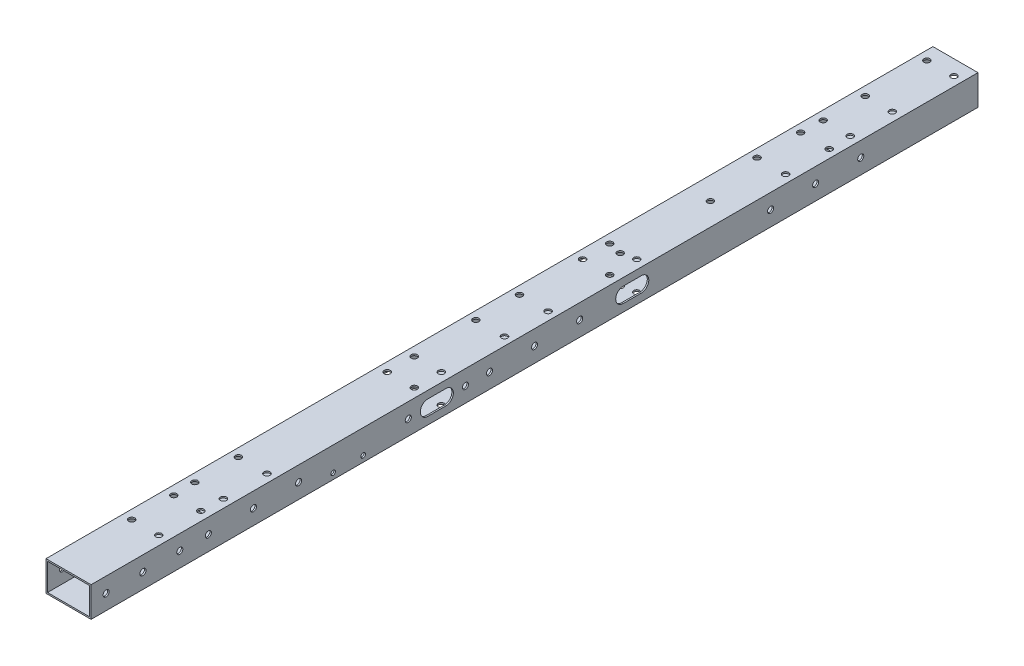
SolidWorks part; units mm, degrees
material "6063-T5"
ref_plane "前视基准面" through (0, 0, 0) normal (0, 0, 1) x (1, 0, 0)
ref_plane "上视基准面" through (0, 0, 0) normal (0, 1, 0) x (1, 0, 0)
ref_plane "右视基准面" through (0, 0, 0) normal (1, 0, 0) x (0, 0, -1)
sketch "草图1" plane through (0, 0, 0) normal (0, 0, 1) x (1, 0, 0)
  line L0 (-14, -9) -> (-14, 9)
  line L1 (-15, -10) -> (15, -10)
  line L2 (-15, -10) -> (-15, 10)
  line L3 (-15, 10) -> (15, 10)
  line L4 (15, -10) -> (15, 10)
  line L5 (0, 10) -> (0, -10) construction
  line L6 (-15, 0) -> (15, 0) construction
  line L7 (-14, 9) -> (14, 9)
  line L8 (14, -9) -> (14, 9)
  line L9 (-14, -9) -> (14, -9)
  point P0 (0, 0)
  dimension "D1" = 20
  dimension "D2" = 30
  dimension "D3" = 1
extrude "凸台-拉伸1" add sketch "草图1" along normal mid plane 590
sketch "草图2" [suppressed] plane through (15, 0, 0) normal (1, 0, 0) x (0, 0, -1)
  line L0 (-295, 10) -> (295, 10) construction
  line L1 (209, 10) -> (295, 10)
  line L2 (209, 10) -> (209, -10)
  line L3 (209, -10) -> (295, -10)
  line L4 (295, 10) -> (295, -10)
  dimension "D1" = 86
extrude "切除-拉伸1" [suppressed] cut sketch "草图2" against normal blind 60
sketch "草图4" [suppressed] plane through (0, 10, 0) normal (0, 1, 0) x (1, 0, 0)
  circle A0 centre (0, 0) radius 5
  dimension "D1" = 10
extrude "切除-拉伸3" [suppressed] cut sketch "草图4" against normal mid plane 64
sketch "草图5" plane through (0, 9, 0) normal (0, -1, 0) x (1, 0, 0)
  line L0 (-15, 295) -> (-15, -295) construction
  line L1 (-9.5, 14.5) -> (9.5, 14.5) construction
  line L2 (-9.5, 14.5) -> (-9.5, -14.5) construction
  line L3 (-9.5, -14.5) -> (9.5, -14.5) construction
  line L4 (9.5, 14.5) -> (9.5, -14.5) construction
  line L5 (-9.5, 14.5) -> (9.5, -14.5) construction
  line L6 (-9.5, -14.5) -> (9.5, 14.5) construction
  line L7 (-9.5, 201.5) -> (9.5, 201.5) construction
  line L8 (-9.5, 201.5) -> (-9.5, 172.5) construction
  line L13 (-9.5, 172.5) -> (9.5, 172.5) construction
  line L14 (9.5, 201.5) -> (9.5, 172.5) construction
  line L15 (-15, 295) -> (15, 295) construction
  line L16 (15, 295) -> (15, -295) construction
  line L17 (-9.5, -172.5) -> (9.5, -172.5) construction
  line L18 (-9.5, -172.5) -> (-9.5, -201.5) construction
  line L19 (-9.5, -201.5) -> (9.5, -201.5) construction
  line L20 (9.5, -172.5) -> (9.5, -201.5) construction
  line L21 (-15, -295) -> (15, -295) construction
  circle A4 centre (9.5, -201.5) radius 1.65 construction
  circle A5 centre (9.5, -172.5) radius 1.65 construction
  circle A6 centre (-9.5, -201.5) radius 1.65 construction
  circle A7 centre (-9.5, -172.5) radius 1.65 construction
  circle A8 centre (-9.5, -172.5) radius 2.025
  circle A9 centre (9.5, -172.5) radius 2.025
  circle A10 centre (-9.5, -201.5) radius 2.025
  circle A11 centre (9.5, -201.5) radius 2.025
  circle A20 centre (9.5, 172.5) radius 1.65 construction
  circle A21 centre (-9.5, 172.5) radius 1.65 construction
  circle A22 centre (9.5, 201.5) radius 1.65 construction
  circle A23 centre (-9.5, 201.5) radius 1.65 construction
  circle A24 centre (9.5, -14.5) radius 1.65 construction
  circle A25 centre (9.5, 14.5) radius 1.65 construction
  circle A26 centre (-9.5, -14.5) radius 1.65 construction
  circle A27 centre (-9.5, 14.5) radius 1.65 construction
  circle A28 centre (-9.5, -14.5) radius 2.025
  circle A29 centre (9.5, -14.5) radius 2.025
  circle A30 centre (-9.5, 14.5) radius 2.025
  circle A31 centre (9.5, 14.5) radius 2.025
  circle A32 centre (-9.5, 172.5) radius 2.025
  circle A33 centre (-9.5, 201.5) radius 2.025
  circle A34 centre (9.5, 201.5) radius 2.025
  circle A35 centre (9.5, 172.5) radius 2.025
  point P1 (0, 0)
  point P3 (-9.5, 187)
  dimension "D1" = 4.05
  dimension "D2" = 29
  dimension "D5" = 29
  dimension "D3" = 19
  dimension "D4" = 19
  dimension "D6" = 5.5
  dimension "D7" = 93.5
  dimension "D8" = 5.5
  dimension "D9" = 5.5
  dimension "D10" = 122.5
  dimension "D11" = 29
extrude "切除-拉伸4" cut sketch "草图5" against normal mid plane 10
sketch "草图7" plane through (0, -9, 0) normal (0, 1, 0) x (1, 0, 0)
  circle A0 centre (-9.5, 201.5) radius 3.8
  circle A1 centre (9.5, 201.5) radius 3.8
  circle A2 centre (-9.5, 172.5) radius 3.8
  circle A3 centre (9.5, 172.5) radius 3.8
  circle A4 centre (-9.5, 14.5) radius 3.8
  circle A5 centre (9.5, 14.5) radius 3.8
  circle A6 centre (-9.5, -14.5) radius 3.8
  circle A7 centre (9.5, -14.5) radius 3.8
  circle A8 centre (-9.5, -172.5) radius 3.8
  circle A9 centre (9.5, -172.5) radius 3.8
  circle A10 centre (-9.5, -201.5) radius 3.8
  circle A11 centre (9.5, -201.5) radius 3.8
  dimension "D1" = 7.6
extrude "切除-拉伸5" cut sketch "草图7" against normal mid plane 10
sketch "草图8" [suppressed] plane through (15, 0, 0) normal (1, 0, 0) x (0, 0, -1)
  circle A0 centre (-151, 0) radius 2.025 construction
  circle A1 centre (-185, 0) radius 2.025 construction
  circle A2 centre (-219, 0) radius 2.025 construction
  circle A3 centre (-151, 0) radius 2.025
  circle A4 centre (-185, 0) radius 2.025
  circle A5 centre (-219, 0) radius 2.025
  circle A6 centre (36, 0) radius 2.025 construction
  circle A7 centre (2, 0) radius 2.025 construction
  circle A8 centre (-32, 0) radius 2.025 construction
  circle A9 centre (36, 0) radius 2.025
  circle A10 centre (2, 0) radius 2.025
  circle A11 centre (-32, 0) radius 2.025
extrude "切除-拉伸6" [suppressed] cut sketch "草图8" against normal blind 74
sketch "草图9" [suppressed] plane through (-15, 0, 0) normal (-1, 0, 0) x (0, 0, 1)
  circle A0 centre (-155, 0) radius 2.025 construction
  circle A1 centre (-189, 5) radius 1.525 construction
  circle A2 centre (-203, 0) radius 2.025 construction
  circle A3 centre (-155, 0) radius 2.025
  circle A4 centre (-189, 5) radius 1.525
  circle A5 centre (-203, 0) radius 2.025
extrude "切除-拉伸7" [suppressed] cut sketch "草图9" against normal blind 114
sketch "草图10" [suppressed] plane through (0, -10, 0) normal (0, -1, 0) x (1, 0, 0)
  circle A0 centre (0, -75) radius 2.025 construction
  circle A1 centre (0, -109) radius 2.025 construction
  circle A2 centre (0, -143) radius 2.025 construction
  circle A3 centre (0, -75) radius 2.025
  circle A4 centre (0, -109) radius 2.025
  circle A5 centre (0, -143) radius 2.025
extrude "切除-拉伸8" [suppressed] cut sketch "草图10" against normal blind 70
sketch "草图11" plane through (15, 0, 0) normal (1, 0, 0) x (0, 0, -1)
  line L0 (-295, -10) -> (-295, 10) construction
  line L1 (-295, 10) -> (295, 10) construction
  circle A9 centre (-236, 0) radius 2.025 construction
  circle A10 centre (-260.5, 0) radius 2.025 construction
  circle A11 centre (-285, 0) radius 2.025 construction
  circle A12 centre (217, 0) radius 2.025
  circle A13 centre (187, 0) radius 2.025
  circle A14 centre (157, 0) radius 2.025
  circle A15 centre (30, 0) radius 2.025
  circle A16 centre (0, 0) radius 2.025
  circle A17 centre (-30, 0) radius 2.025
  circle A18 centre (-157, 0) radius 2.025
  circle A19 centre (-187, 0) radius 2.025
  circle A20 centre (-217, 0) radius 2.025
  circle A21 centre (-236, 0) radius 2.025
  circle A22 centre (-260.5, 0) radius 2.025
  circle A23 centre (-285, 0) radius 2.025
  dimension "D1" = 30
  dimension "D3" = 78
  dimension "D4" = 30
  dimension "D5" = 30
  dimension "D6" = 10
  dimension "D7" = 127
  dimension "D8" = 127
  dimension "D9" = 30
  dimension "D10" = 30
  dimension "D2" = 30
extrude "切除-拉伸9" cut sketch "草图11" against normal blind 113
sketch "草图12" [suppressed] plane through (0, 10, 0) normal (0, 1, 0) x (1, 0, 0)
  circle A0 centre (0, 36.5) radius 2.025 construction
  circle A1 centre (0, 18.5) radius 2.025 construction
  circle A2 centre (0, 36.5) radius 2.025
  circle A3 centre (0, 18.5) radius 2.025
extrude "切除-拉伸10" [suppressed] cut sketch "草图12" against normal blind 80
sketch "草图13" [suppressed] plane through (-15, 0, 0) normal (-1, 0, 0) x (0, 0, 1)
  circle A0 centre (28, 0) radius 2.025 construction
  circle A1 centre (3.5, 0) radius 2.025 construction
  circle A2 centre (28, 0) radius 2.025
  circle A3 centre (3.5, 0) radius 2.025
extrude "切除-拉伸11" [suppressed] cut sketch "草图13" against normal blind 80
sketch "草图14" [suppressed] plane through (0, -9, 0) normal (0, 1, 0) x (1, 0, 0)
  circle A0 centre (-7.5, 45.55) radius 1.5 construction
  circle A1 centre (-7.5, 35.55) radius 1.5 construction
  circle A2 centre (7.5, 45.55) radius 1.5 construction
  circle A3 centre (7.5, 35.55) radius 1.5 construction
  circle A4 centre (7.5, 90.55) radius 1.5 construction
  circle A5 centre (7.5, 80.55) radius 1.5 construction
  circle A6 centre (-7.5, 90.55) radius 1.5 construction
  circle A7 centre (-7.5, 80.55) radius 1.5 construction
  circle A8 centre (-7.5, 45.55) radius 1.5
  circle A9 centre (-7.5, 35.55) radius 1.5
  circle A10 centre (7.5, 45.55) radius 1.5
  circle A11 centre (7.5, 35.55) radius 1.5
  circle A12 centre (7.5, 90.55) radius 1.5
  circle A13 centre (7.5, 80.55) radius 1.5
  circle A14 centre (-7.5, 90.55) radius 1.5
  circle A15 centre (-7.5, 80.55) radius 1.5
extrude "切除-拉伸12" [suppressed] cut sketch "草图14" against normal blind 10
sketch "草图15" [suppressed] plane through (0, -10, 0) normal (0, -1, 0) x (1, 0, 0)
  circle A0 centre (9, 66) radius 2.025 construction
  circle A1 centre (-9, 66) radius 2.025 construction
  circle A2 centre (9, 94) radius 2.025 construction
  circle A3 centre (-9, 94) radius 2.025 construction
  circle A4 centre (9, 66) radius 2.025
  circle A5 centre (-9, 66) radius 2.025
  circle A6 centre (9, 94) radius 2.025
  circle A7 centre (-9, 94) radius 2.025
extrude "切除-拉伸13" [suppressed] cut sketch "草图15" against normal up to surface (20 mm away)
sketch "草图16" [suppressed] plane through (-15, 0, 0) normal (-1, 0, 0) x (0, 0, 1)
  line L0 (0, 0) -> (0, 10) construction
  line L1 (84.5, 10) -> (-84.5, 10) construction
  circle A0 centre (59.5, 0) radius 1.525 construction
  circle A1 centre (79.5, 0) radius 1.525 construction
  circle A2 centre (59.5, 0) radius 1.525
  circle A3 centre (79.5, 0) radius 1.525
  circle A4 centre (-79.5, 0) radius 1.525
  circle A5 centre (-59.5, 0) radius 1.525
sketch "草图17" [suppressed] plane through (15, 0, 0) normal (1, 0, 0) x (0, 0, -1)
  circle A0 centre (94, 0) radius 1.525 construction
  circle A1 centre (66, 0) radius 1.525 construction
  circle A2 centre (94, 0) radius 1.525
  circle A3 centre (66, 0) radius 1.525
extrude "切除-拉伸14" [suppressed] cut sketch "草图16" against normal up to surface (30 mm away)
extrude "切除-拉伸15" [suppressed] cut sketch "草图17" against normal up to surface (30 mm away)
sketch "草图18" plane through (0, -10, 0) normal (0, -1, 0) x (1, 0, 0)
  line L0 (-429.5, 50) -> (160.5, 50) construction
  line L1 (-429.5, 80) -> (160.5, 80) construction
  line L2 (-15, 50) -> (15, 50) construction
  line L3 (-15, 80) -> (15, 80) construction
  line L4 (15, 295) -> (15, -295) construction
  line L5 (-15, 295) -> (-15, -295) construction
  line L6 (-15, 80) -> (15, 50) construction
  line L8 (-9, 56) -> (9, 56) construction
  line L9 (-9, 56) -> (-9, 74) construction
  line L10 (-9, 74) -> (9, 74) construction
  line L11 (9, 56) -> (9, 74) construction
  line L12 (0, 74) -> (0, 56) construction
  line L13 (-9, 65) -> (9, 65) construction
  circle A0 centre (-9, 74) radius 2.025
  circle A1 centre (9, 74) radius 2.025
  circle A2 centre (-9, 56) radius 2.025
  circle A3 centre (9, 56) radius 2.025
  point P4 (0, 65)
  dimension "D3" = 4.05
  dimension "D1" = 6
  dimension "D2" = 6
extrude "切除-拉伸16" cut sketch "草图18" against normal blind 90
mirror "镜向1" about plane through (0, 0, 0) normal (0, 0, 1) of "切除-拉伸16"
sketch "草图19" [suppressed] plane through (0, 10, 0) normal (0, 1, 0) x (1, 0, 0)
  line L0 (-15, -275) -> (15, -275) construction
  line L1 (-15, -295) -> (-15, 209) construction
  line L2 (15, -295) -> (-15, -295) construction
  line L3 (15, -295) -> (15, 209) construction
  line L4 (-15, -275) -> (15, -295) construction
  line L6 (-10, -290) -> (10, -290) construction
  line L7 (-10, -290) -> (-10, -280) construction
  line L8 (-10, -280) -> (10, -280) construction
  line L9 (10, -290) -> (10, -280) construction
  line L10 (0, -280) -> (0, -290) construction
  line L11 (-10, -285) -> (10, -285) construction
  circle A0 centre (-10, -285) radius 2.025
  circle A1 centre (10, -285) radius 2.025
  point P6 (0, -285)
  dimension "D4" = 4.05
  dimension "D1" = 20
  dimension "D2" = 5
  dimension "D3" = 5
extrude "切除-拉伸17" [suppressed] cut sketch "草图19" against normal blind 10
sketch "草图20" [suppressed] plane through (0, 10, 0) normal (0, 1, 0) x (1, 0, 0)
  circle A0 centre (-10, -151) radius 2.025 construction
  circle A1 centre (10, -151) radius 2.025 construction
  circle A2 centre (-10, -151) radius 2.025
  circle A3 centre (10, -151) radius 2.025
extrude "切除-拉伸18" [suppressed] cut sketch "草图20" against normal blind 10
sketch "草图21" plane through (15, 0, 0) normal (1, 0, 0) x (0, 0, -1)
  line L0 (-40, 290) -> (-40, -10) construction
  line L1 (-90, 290) -> (-90, -10) construction
  line L2 (-40, 10) -> (-40, -10) construction
  line L3 (-90, 10) -> (-90, -10) construction
  line L4 (-295, 10) -> (295, 10) construction
  line L5 (-90, 10) -> (-40, -10) construction
  line L6 (-84, 0) -> (-46, 0) construction
  circle A0 centre (-46, 0) radius 2.025
  circle A1 centre (-84, 0) radius 2.025
  point P11 (-65, 0)
  dimension "D2" = 4.05
  dimension "D1" = 6
extrude "切除-拉伸19" cut sketch "草图21" against normal blind 126
sketch "草图22" plane through (0, 10, 0) normal (0, 1, 0) x (1, 0, 0)
  line L0 (15, -275) -> (-15, -275) construction
  line L1 (15, -295) -> (15, 295) construction
  line L2 (-15, -295) -> (-15, 295) construction
  line L3 (15, -295) -> (-15, -295) construction
  line L4 (-15, -275) -> (15, -295) construction
  line L5 (-9, -285) -> (9, -285) construction
  line L6 (0, 0) -> (95.2431, 0) construction
  line L7 (-9, 285) -> (9, 285) construction
  line L8 (-15, 275) -> (15, 295) construction
  line L9 (15, 275) -> (-15, 275) construction
  circle A0 centre (9, -285) radius 2.025 construction
  circle A1 centre (-9, -285) radius 2.025 construction
  circle A2 centre (-9, 285) radius 2.025
  circle A3 centre (9, 285) radius 2.025
  point P13 (0, -285)
  point P25 (0, 285)
  dimension "D3" = 4.05
  dimension "D1" = 20
  dimension "D2" = 6
extrude "切除-拉伸20" cut sketch "草图22" against normal blind 10
sketch "草图23" [suppressed] plane through (-15, 0, 0) normal (-1, 0, 0) x (0, 0, 1)
  circle A0 centre (44, 0) radius 2.025 construction
  circle A1 centre (82, 0) radius 2.025 construction
  circle A2 centre (44, 0) radius 2.025
  circle A3 centre (82, 0) radius 2.025
extrude "切除-拉伸21" [suppressed] cut sketch "草图23" against normal blind 70
sketch "草图24" [suppressed] plane through (-15, 0, 0) normal (-1, 0, 0) x (0, 0, 1)
  circle A0 centre (44, 0) radius 4
  circle A1 centre (82, 0) radius 4
  dimension "D1" = 8
extrude "切除-拉伸22" [suppressed] cut sketch "草图24" against normal blind 10
sketch "草图25" [suppressed] plane through (0, -10, 0) normal (0, -1, 0) x (1, 0, 0)
  line L0 (-15, 46.025) -> (-15, 41.975) construction
  line L1 (-15, 84.025) -> (-15, 79.975) construction
  line L2 (-15, 46.025) -> (-15, 41.975) construction
  line L3 (-15, 84.025) -> (-15, 79.975) construction
  line L4 (-15, 82) -> (15, 82) construction
  line L5 (15, 295) -> (15, -209) construction
  line L6 (-15, 44) -> (15, 82) construction
  line L7 (0, 45.5) -> (0, 80.5) construction
  line L8 (-7, 45.5) -> (-7, 80.5)
  line L9 (7, 45.5) -> (7, 80.5)
  arc A0 (-7, 45.5) -> (7, 45.5) centre (0, 45.5) ccw
  arc A1 (7, 80.5) -> (-7, 80.5) centre (0, 80.5) ccw
  point P11 (0, 63)
  dimension "D1" = 7
  dimension "D2" = 35
extrude "切除-拉伸23" [suppressed] cut sketch "草图25" against normal blind 10 from surface
sketch "草图26" plane through (0, -10, 0) normal (0, -1, 0) x (1, 0, 0)
  line L0 (-11, 144) -> (-11, 124) construction
  line L1 (-15, 295) -> (-15, -295) construction
  line L2 (0, 0) -> (0, 192.5481) construction
  line L3 (11, 144) -> (11, 124) construction
  circle A0 centre (-11, 124) radius 1.525
  circle A1 centre (-11, 144) radius 1.525
  circle A2 centre (-9, 74) radius 2.025 construction
  circle A3 centre (11, 144) radius 1.525
  circle A4 centre (11, 124) radius 1.525
  dimension "D3" = 3.05
  dimension "D4" = 50
  dimension "D1" = 20
  dimension "D2" = 4
extrude "切除-拉伸24" cut sketch "草图26" against normal blind 10
sketch "草图27" plane through (-15, 0, 0) normal (-1, 0, 0) x (0, 0, 1)
  circle A0 centre (114, -6) radius 1.25 construction
  circle A1 centre (134, -6) radius 1.25 construction
  circle A2 centre (114, -6) radius 1.25 construction
  circle A3 centre (134, -6) radius 1.25 construction
  circle A4 centre (134, -6) radius 1.525
  circle A5 centre (114, -6) radius 1.525
  dimension "D1" = 3.05
extrude "切除-拉伸25" cut sketch "草图27" against normal blind 100
sketch "草图28" plane through (15, 0, 0) normal (1, 0, 0) x (0, 0, -1)
  line L0 (-53.975, 10) -> (-58.025, 10) construction
  line L1 (-71.975, 10) -> (-76.025, 10) construction
  line L2 (-53.975, 10) -> (-58.025, 10) construction
  line L3 (-71.975, 10) -> (-76.025, 10) construction
  line L4 (-74, 10) -> (-74, -10) construction
  line L5 (-295, -10) -> (295, -10) construction
  line L6 (-56, 10) -> (-56, -10) construction
  line L7 (-74, 0) -> (-56, 0) construction
  line L8 (-71, 0) -> (-59, 0) construction
  line L9 (-71, 5) -> (-59, 5)
  line L10 (-71, -5) -> (-59, -5)
  arc A0 (-71, 5) -> (-71, -5) centre (-71, 0) ccw
  arc A1 (-59, -5) -> (-59, 5) centre (-59, 0) ccw
  point P14 (-65, 0)
  dimension "D1" = 5
  dimension "D2" = 12
extrude "切除-拉伸26" cut sketch "草图28" against normal blind 100
mirror "镜向2" about plane through (0, 0, 0) normal (0, 0, 1) of "切除-拉伸26"
sketch "草图29" [suppressed] plane through (0, 10, 0) normal (0, 1, 0) x (1, 0, 0)
  circle A0 centre (-5.25, 9.0933) radius 1.7 construction
  circle A1 centre (5.25, 9.0933) radius 1.7 construction
  circle A2 centre (5.25, -9.0933) radius 1.7 construction
  circle A3 centre (-5.25, -9.0933) radius 1.7 construction
  circle A4 centre (-5.25, 9.0933) radius 1.7 construction
  circle A5 centre (5.25, 9.0933) radius 1.7 construction
  circle A6 centre (5.25, -9.0933) radius 1.7 construction
  circle A7 centre (-5.25, -9.0933) radius 1.7 construction
  circle A8 centre (5.25, 9.0933) radius 1.525
  circle A9 centre (-5.25, 9.0933) radius 1.525
  circle A10 centre (-5.25, -9.0933) radius 1.525
  circle A11 centre (5.25, -9.0933) radius 1.525
  dimension "D1" = 3.05
extrude "切除-拉伸27" [suppressed] cut sketch "草图29" against normal blind 60
sketch "草图30" [suppressed] plane through (15, 0, 0) normal (1, 0, 0) x (0, 0, -1)
  line L0 (10.6183, 10) -> (7.5683, 10) construction
  line L1 (-7.5683, 10) -> (-10.6183, 10) construction
  line L2 (10.6183, 10) -> (7.5683, 10) construction
  line L3 (-7.5683, 10) -> (-10.6183, 10) construction
  line L4 (-9.0933, 10) -> (-9.0933, -10) construction
  line L5 (-84.5, -10) -> (84.5, -10) construction
  line L6 (9.0933, 10) -> (9.0933, -10) construction
  line L7 (-6.5, 0) -> (6.5, 0) construction
  line L8 (-6.5, 5) -> (6.5, 5)
  line L9 (-6.5, -5) -> (6.5, -5)
  arc A0 (-6.5, 5) -> (-6.5, -5) centre (-6.5, 0) ccw
  arc A1 (6.5, -5) -> (6.5, 5) centre (6.5, 0) ccw
  point P12 (0, 0)
  dimension "D1" = 5
  dimension "D2" = 13
extrude "切除-拉伸28" [suppressed] cut sketch "草图30" against normal blind 60
sketch "草图31" plane through (0, 10, 0) normal (0, 1, 0) x (1, 0, 0)
  circle A4 centre (0, 72) radius 2.025 construction
  circle A5 centre (0, 132) radius 2.025 construction
  circle A6 centre (0, 72) radius 2.025
  circle A7 centre (0, 132) radius 2.025
extrude "切除-拉伸29" cut sketch "草图31" against normal blind 50
sketch "草图32" plane through (-15, 0, 0) normal (-1, 0, 0) x (0, 0, 1)
  circle A0 centre (46, 0) radius 3.75
  circle A1 centre (84, 0) radius 3.75
  dimension "D1" = 7.5
extrude "切除-拉伸30" cut sketch "草图32" against normal blind 10
sketch "草图33" [suppressed] plane through (0, 10, 0) normal (0, 1, 0) x (1, 0, 0)
  line L0 (0, -171) -> (0, -201) construction
  line L1 (6, -171) -> (6, -201)
  line L2 (-6, -171) -> (-6, -201)
  arc A0 (6, -171) -> (-6, -171) centre (0, -171) ccw
  arc A1 (-6, -201) -> (6, -201) centre (0, -201) ccw
  circle A2 centre (10, -151) radius 2.025 construction
  point P3 (0, -186)
  dimension "D2" = 6
  dimension "D1" = 20
  dimension "D3" = 30
extrude "切除-拉伸31" [suppressed] cut sketch "草图33" against normal up to surface (20 mm away)
sketch "草图34" [suppressed] plane through (0, 10, 0) normal (0, 1, 0) x (1, 0, 0)
  line L0 (15, -0.025) -> (15, 4.025) construction
  line L1 (15, -0.025) -> (15, 4.025) construction
  line L2 (15, 2) -> (-15, 2) construction
  line L3 (-15, -295) -> (-15, 209) construction
  line L4 (0, 2) -> (0, 17) construction
  circle A0 centre (0, 17) radius 1.525
  circle A1 centre (0, -13) radius 1.525
  dimension "D2" = 3.05
  dimension "D1" = 15
extrude "切除-拉伸32" [suppressed] cut sketch "草图34" against normal blind 50
sketch "草图36" plane through (0, 10, 0) normal (0, 1, 0) x (1, 0, 0)
  line L0 (15, -295) -> (15, 295) construction
  line L1 (-9, 244) -> (9, 244) construction
  line L2 (-9, 244) -> (-9, 216) construction
  line L3 (-9, 216) -> (9, 216) construction
  line L4 (9, 244) -> (9, 216) construction
  line L5 (-15, -295) -> (-15, 295) construction
  line L6 (15, 295) -> (-15, 295) construction
  circle A4 centre (-9, 244) radius 2.025
  circle A5 centre (-9, 216) radius 2.025
  circle A6 centre (9, 216) radius 2.025
  circle A7 centre (9, 244) radius 2.025
  dimension "D5" = 4.05
  dimension "D1" = 6
  dimension "D2" = 6
  dimension "D3" = 28
  dimension "D4" = 79
extrude "切除-拉伸33" cut sketch "草图36" against normal blind 37
sketch "草图37" plane through (0, -10, 0) normal (0, -1, 0) x (1, 0, 0)
  circle A0 centre (-9, -216) radius 3.8
  circle A1 centre (9, -216) radius 3.8
  circle A2 centre (-9, -244) radius 3.8
  circle A3 centre (9, -244) radius 3.8
  circle A4 centre (-9.5, -201.5) radius 3.8 construction
extrude "切除-拉伸34" cut sketch "草图37" against normal blind 10
mirror "镜向3" about plane through (0, 0, 0) normal (0, 0, 1) of "切除-拉伸34", "切除-拉伸33"
